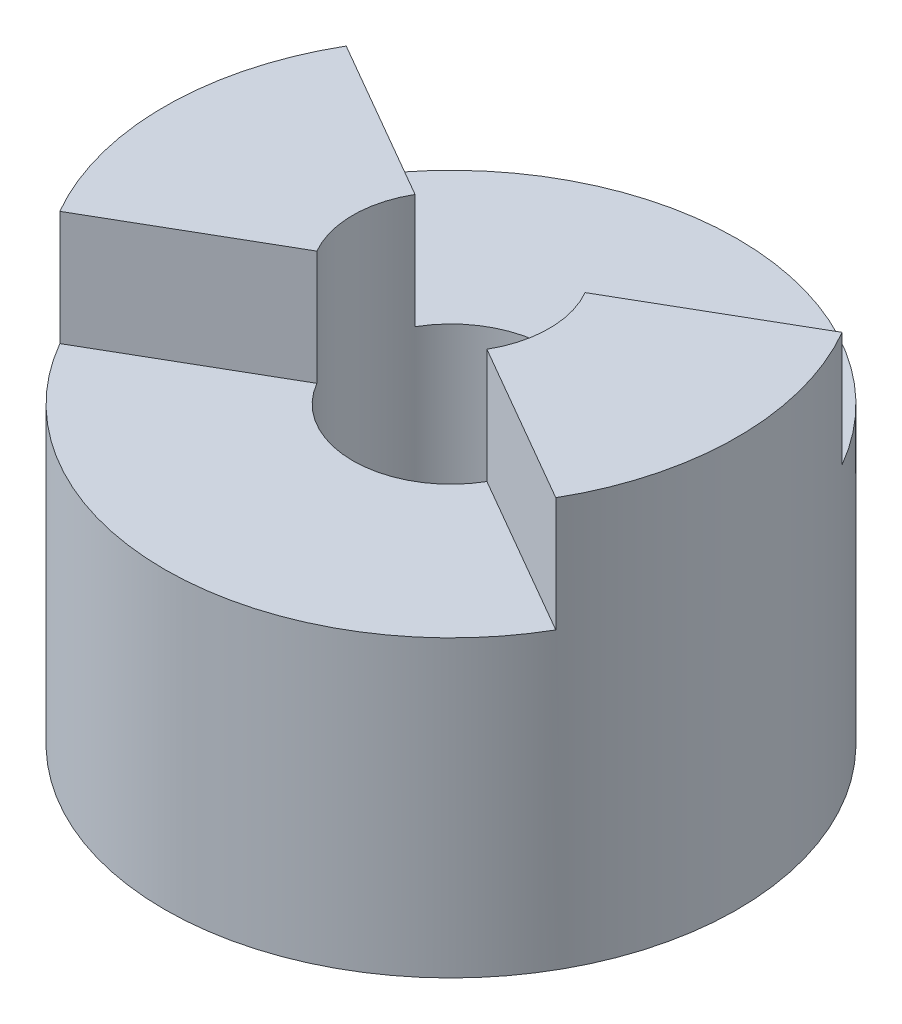
SolidWorks part; units mm, degrees
ref_plane "Front Plane" through (0, 0, 0) normal (0, 0, 1) x (1, 0, 0)
ref_plane "Top Plane" through (0, 0, 0) normal (0, 1, 0) x (1, 0, 0)
ref_plane "Right Plane" through (0, 0, 0) normal (1, 0, 0) x (0, 0, -1)
sketch "Sketch1" plane through (0, 0, 0) normal (0, 1, 0) x (1, 0, 0)
  circle A0 centre (0, 0) radius 35
  circle A1 centre (0, 0) radius 12
  dimension "D1" = 70
  dimension "D2" = 24
extrude "Boss-Extrude1" add sketch "Sketch1" along normal blind 50
sketch "Sketch2" plane through (0, 50, 0) normal (0, 1, 0) x (1, 0, 0)
  line L0 (0, 0) -> (45.0155, 0) construction
  line L1 (0, 0) -> (0, -60.2355) construction
  line L2 (10.3923, -6) -> (30.3109, -17.5)
  line L3 (-10.3923, -6) -> (-30.3109, -17.5)
  circle A0 centre (0, 0) radius 35 construction
  arc A1 (-30.3109, -17.5) -> (30.3109, -17.5) centre (0, 0) ccw
  circle A2 centre (0, 0) radius 12 construction
  arc A3 (-10.3923, -6) -> (10.3923, -6) centre (0, 0) ccw
  dimension "D1" = 120
extrude "Cut-Extrude1" cut sketch "Sketch2" against normal offset from surface (14 mm away) 36 up to face at (0, 0, 35)
ref_axis "Axis1" through (0, 50, 0) along (0, -1, 0)
mirror "Mirror1" about plane through (0, 0, 0) normal (0, 0, 1) of "Cut-Extrude1"
